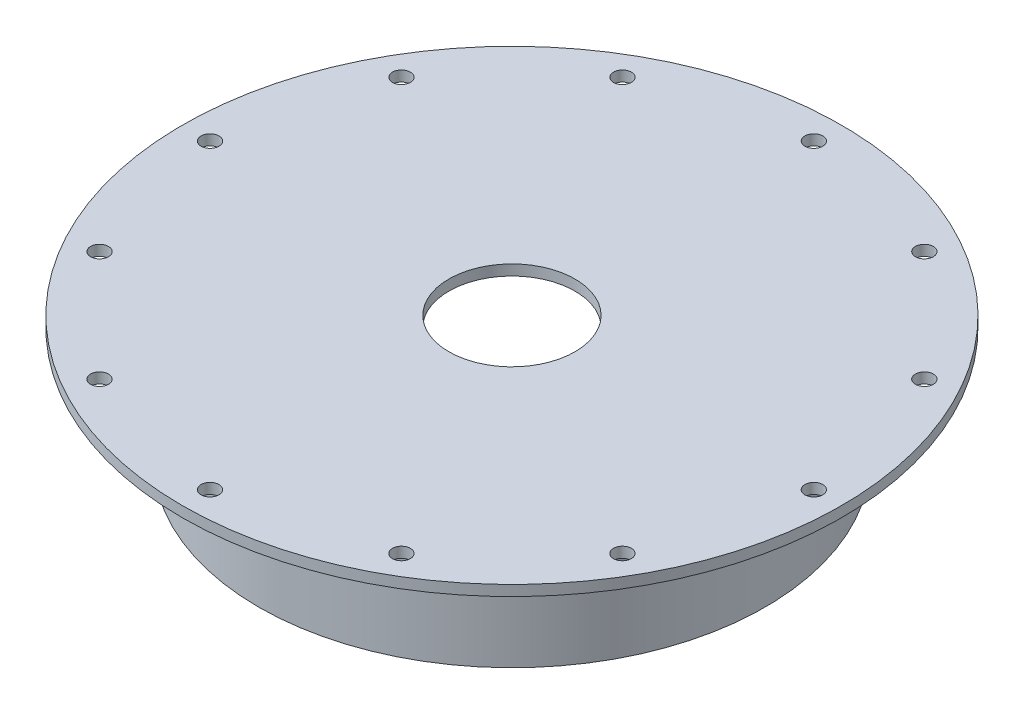
SolidWorks part; units mm, degrees
material "6063-T6"
ref_plane "Front Plane" through (0, 0, 0) normal (0, 0, 1) x (1, 0, 0)
ref_plane "Top Plane" through (0, 0, 0) normal (0, 1, 0) x (1, 0, 0)
ref_plane "Right Plane" through (0, 0, 0) normal (1, 0, 0) x (0, 0, -1)
ref_axis "Axis1" through (0, 55, 0) along (0, -1, 0)
sketch "Sketch1" plane through (0, 0, 0) normal (0, 0, 1) x (1, 0, 0)
  line L0 (-49.784, 0) -> (-41.4274, 0)
  line L1 (0, 55) -> (0, -55) construction
  line L2 (-49.784, 0) -> (-49.784, 1.5875)
  line L3 (-49.784, 1.5875) -> (-9.525, 1.5875)
  line L4 (-49.784, 1.5875) -> (-9.525, 1.5875) construction
  line L5 (-9.525, 1.5875) -> (-9.525, 0)
  line L6 (-9.525, 0) -> (0, 0) construction
  line L7 (-49.784, 0) -> (-49.784, 1.5875) construction
  line L8 (-9.525, 1.5875) -> (-9.525, 0) construction
  line L9 (-38.2524, -3.175) -> (-38.2524, -17.4625)
  line L10 (-38.2524, -17.4625) -> (-35.0774, -17.4625)
  line L11 (-35.0774, -17.4625) -> (-35.0774, -3.175)
  line L12 (-31.9024, 0) -> (-9.525, 0)
  line L13 (0, -201000) -> (0, 249000) construction
  arc A0 (-35.0774, -3.175) -> (-31.9024, 0) centre (-31.9024, -3.175) cw
  arc A1 (-38.2524, -3.175) -> (-41.4274, 0) centre (-41.4274, -3.175) ccw
  point P18 (-35.0774, 0)
  dimension "D4" = 3.175
  dimension "D5" = 3.175
  dimension "D1" = 3.175
  dimension "D2" = 38.2524
  dimension "D3" = 17.4625
revolve "Revolve1" add sketch "Sketch1" angle 360 about axis through (0, 55, 0) along (0, -1, 0)
ref_plane "Hole Location Plane" through (0, 3.175, 0) normal (0, 1, 0) x (1, 0, 0)
sketch "Hole Location" plane through (0, 3.175, 0) normal (0, 1, 0) x (1, 0, 0)
  line L0 (0, 0) -> (-45.6057, 0) construction
  circle A0 centre (0, 0) radius 45.6057 construction
  dimension "D1" = 91.2114
hole_wizard "#36 (0.1065) Diameter Hole1" positions "Sketch4" profile "Sketch5" hole size "#36" standard "ANSI Inch" end condition through all
sketch "Sketch4" plane through (0, 1.5875, 0) normal (0, 1, 0) x (1, 0, 0)
  point P0 (-45.6057, 0)
sketch "Sketch5" plane through (-45.6057, 1.5875, 0) normal (1, 0, 0) x (0, 0, 1)
  line L0 (0, 0) -> (0, 19.05)
  line L1 (0, 19.05) -> (1.3525, 19.05)
  line L2 (1.3525, 19.05) -> (1.3525, 0)
  line L5 (1.3525, 0) -> (0, 0)
  line L11 (0, -6.35) -> (0, 107.95) construction
  dimension "Thru Hole Dia." = 2.7051
  dimension "Thru Hole Depth" = 19.05
pattern_circular "CirPattern1" count 12 every 30 about axis through (0, 55, 0) along (0, -1, 0) of "#36 (0.1065) Diameter Hole1"
equation "\"D1@Hole Location\"=\"TANK DIAMETER@Cryo Tank.Assembly\"+\"GASKET SEAT THICKNESS@Cryo Tank.Assembly\"+\"LINER THICKNESS@Cryo Tank.Assembly\"+\"SHRINK FIT DELTA@Cryo Tank.Assembly\""
equation "\"D2@Sketch1\"=\"TANK DIAMETER@Cryo Tank.Assembly\"/2+\"SHRINK FIT DELTA@Cryo Tank.Assembly\""
equation "\"D3@Sketch1\"=0.5+0.125+0.0625"
